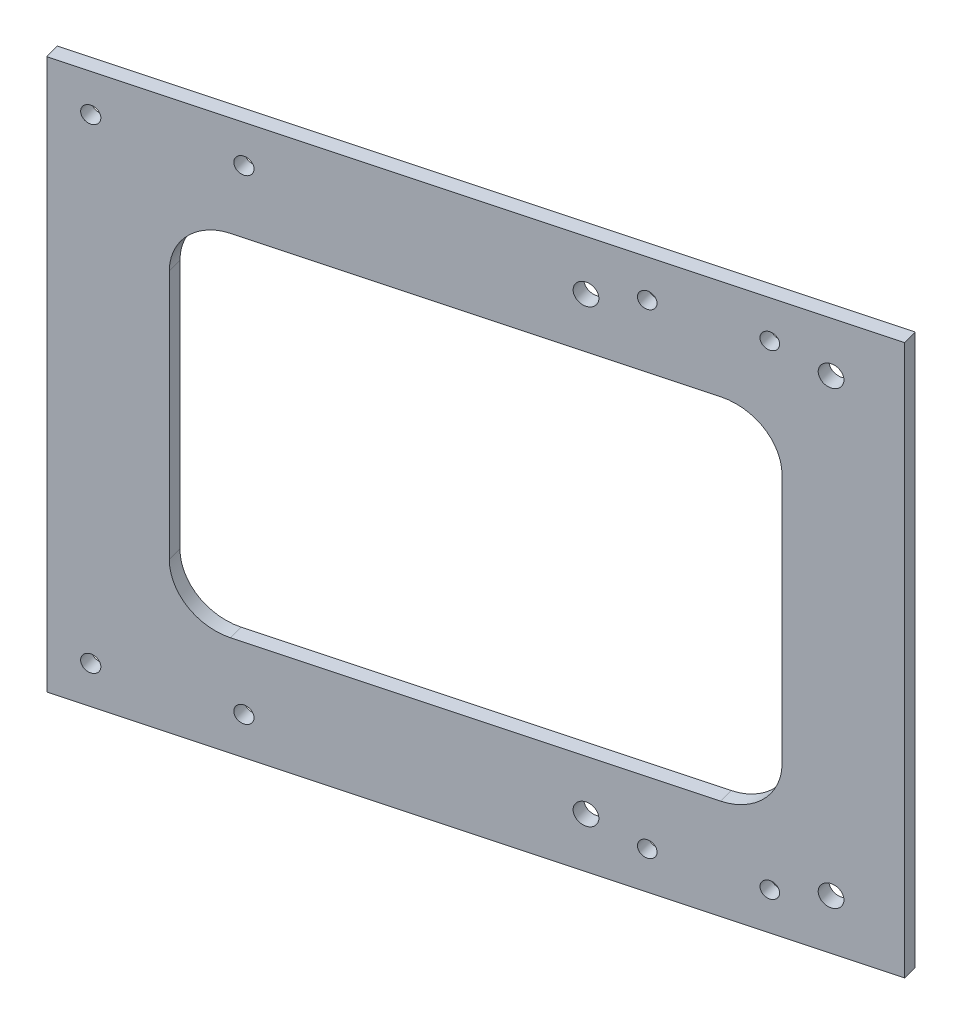
SolidWorks part; units mm, degrees
ref_plane "前视基准面" through (0, 0, 0) normal (0, 0, 1) x (1, 0, 0)
ref_plane "上视基准面" through (0, 0, 0) normal (0, 1, 0) x (1, 0, 0)
ref_plane "右视基准面" through (0, 0, 0) normal (1, 0, 0) x (0, 0, -1)
sketch "Sketch2" plane through (-8.5359, 0, -31.8565) normal (0.2588, 0, 0.9659) x (0.9659, 0, -0.2588)
  line L0 (48.5195, 100.0044) -> (48.5195, -9.9956)
  line L1 (48.5195, -9.9956) -> (188.5195, -9.9956)
  line L2 (188.5195, -9.9956) -> (188.5195, 100.0044)
  line L3 (188.5195, 100.0044) -> (48.5195, 100.0044)
  line L5 (78.5195, 80.0044) -> (158.5195, 80.0044)
  line L6 (68.5195, 70.0044) -> (68.5195, 20.0044)
  line L7 (78.5195, 10.0044) -> (158.5195, 10.0044)
  line L8 (168.5195, 70.0044) -> (168.5195, 20.0044)
  arc A0 (158.5195, 10.0044) -> (168.5195, 20.0044) centre (158.5195, 20.0044) ccw
  arc A1 (68.5195, 20.0044) -> (78.5195, 10.0044) centre (78.5195, 20.0044) ccw
  arc A2 (158.5195, 80.0044) -> (168.5195, 70.0044) centre (158.5195, 70.0044) cw
  arc A3 (78.5195, 80.0044) -> (68.5195, 70.0044) centre (78.5195, 70.0044) ccw
  arc A4 (54.0432, -2.4956) -> (57.3432, -2.4956) centre (55.6932, -2.4956) ccw construction
  arc A5 (57.3432, -2.4956) -> (54.0432, -2.4956) centre (55.6932, -2.4956) ccw construction
  arc A6 (79.0432, -2.4956) -> (82.3432, -2.4956) centre (80.6932, -2.4956) ccw construction
  arc A7 (82.3432, -2.4956) -> (79.0432, -2.4956) centre (80.6932, -2.4956) ccw construction
  arc A8 (79.0432, 92.5044) -> (82.3432, 92.5044) centre (80.6932, 92.5044) ccw construction
  arc A9 (82.3432, 92.5044) -> (79.0432, 92.5044) centre (80.6932, 92.5044) ccw construction
  arc A10 (54.0432, 92.5044) -> (57.3432, 92.5044) centre (55.6932, 92.5044) ccw construction
  arc A11 (57.3432, 92.5044) -> (54.0432, 92.5044) centre (55.6932, 92.5044) ccw construction
  arc A12 (54.0432, -2.4956) -> (57.3432, -2.4956) centre (55.6932, -2.4956) ccw
  arc A13 (57.3432, -2.4956) -> (54.0432, -2.4956) centre (55.6932, -2.4956) ccw
  arc A14 (79.0432, -2.4956) -> (82.3432, -2.4956) centre (80.6932, -2.4956) ccw
  arc A15 (82.3432, -2.4956) -> (79.0432, -2.4956) centre (80.6932, -2.4956) ccw
  arc A16 (79.0432, 92.5044) -> (82.3432, 92.5044) centre (80.6932, 92.5044) ccw
  arc A17 (82.3432, 92.5044) -> (79.0432, 92.5044) centre (80.6932, 92.5044) ccw
  arc A18 (54.0432, 92.5044) -> (57.3432, 92.5044) centre (55.6932, 92.5044) ccw
  arc A19 (57.3432, 92.5044) -> (54.0432, 92.5044) centre (55.6932, 92.5044) ccw
  circle A20 centre (166.5195, 92.5044) radius 1.6 construction
  circle A21 centre (146.5195, 92.5044) radius 1.6 construction
  circle A22 centre (146.5195, -2.4956) radius 1.6 construction
  circle A23 centre (166.5195, -2.4956) radius 1.6 construction
  circle A24 centre (176.5195, 0.0044) radius 2.1 construction
  circle A25 centre (136.5195, 0.0044) radius 2.1 construction
  circle A26 centre (176.5195, 90.0044) radius 2.1 construction
  circle A27 centre (136.5195, 90.0044) radius 2.1 construction
  circle A28 centre (166.5195, 92.5044) radius 1.6
  circle A29 centre (146.5195, 92.5044) radius 1.6
  circle A30 centre (146.5195, -2.4956) radius 1.6
  circle A31 centre (166.5195, -2.4956) radius 1.6
  circle A32 centre (176.5195, 0.0044) radius 2.1
  circle A33 centre (136.5195, 0.0044) radius 2.1
  circle A34 centre (176.5195, 90.0044) radius 2.1
  circle A35 centre (136.5195, 90.0044) radius 2.1
  dimension "D6" = 10
  dimension "D1" = 140
  dimension "D2" = 20
  dimension "D3" = 20
  dimension "D4" = 20
  dimension "D5" = 20
extrude "Extrude1" add sketch "Sketch2" along normal blind 3
